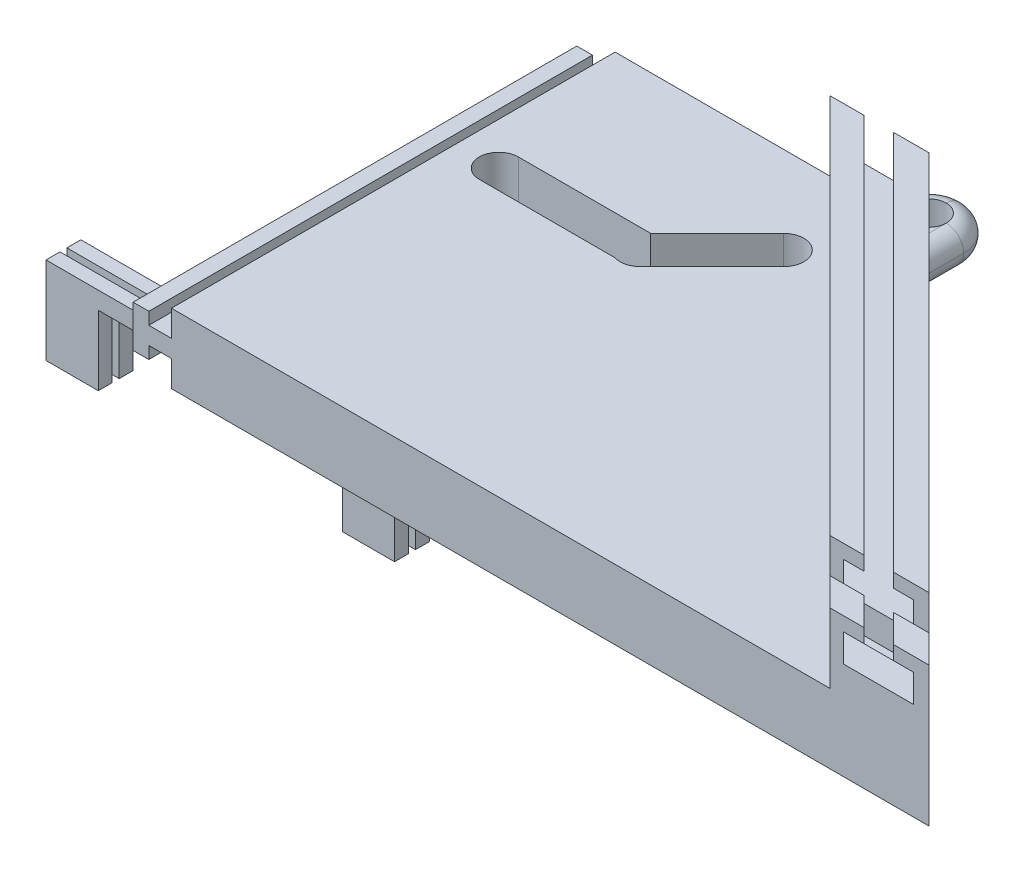
SolidWorks part; units mm, degrees
ref_plane "Front Plane" through (0, 0, 0) normal (0, 0, 1) x (1, 0, 0)
ref_plane "Top Plane" through (0, 0, 0) normal (0, 1, 0) x (1, 0, 0)
ref_plane "Right Plane" through (0, 0, 0) normal (1, 0, 0) x (0, 0, -1)
sketch "Sketch1" plane through (0, 0, 0) normal (0, 1, 0) x (1, 0, 0)
  line L0 (-11.6729, -34.564) -> (96.9667, -34.564)
  line L1 (96.9667, -34.564) -> (33.3271, 29.0756)
  line L2 (33.3271, 29.0756) -> (-11.6729, 29.0756)
  line L3 (-11.6729, 29.0756) -> (-11.6729, -34.564)
  dimension "D1" = 45
  dimension "D2" = 45
  dimension "D3" = 90
extrude "Boss-Extrude1" add sketch "Sketch1" along normal blind 10
sketch "Sketch2" plane through (0, 0, 34.564) normal (0, 0, 1) x (1, 0, 0)
  line L0 (-11.6729, 3.75) -> (-14.9229, 3.75)
  line L1 (-11.6729, 10) -> (-11.6729, 0) construction
  line L2 (-14.9229, 3.75) -> (-14.9229, 2)
  line L3 (-14.9229, 2) -> (-17.1729, 2)
  line L4 (-17.1729, 2) -> (-17.1729, 8)
  line L5 (-17.1729, 8) -> (-14.9229, 8)
  line L6 (-14.9229, 8) -> (-14.9229, 6.25)
  line L7 (-14.9229, 6.25) -> (-11.6729, 6.25)
  line L8 (-11.6729, 6.25) -> (-11.6729, 3.75)
  line L9 (-11.6729, 0) -> (96.9667, 0) construction
  line L10 (-11.6729, 10) -> (96.9667, 10) construction
  dimension "D1" = 3.75
  dimension "D2" = 3.75
  dimension "D3" = 1.75
  dimension "D4" = 1.75
  dimension "D5" = 2.25
  dimension "D6" = 3.25
  dimension "D7" = 3.25
extrude "Boss-Extrude3" add sketch "Sketch2" against normal blind 65
sketch "Sketch3" plane through (0, 8, 0) normal (0, 1, 0) x (1, 0, 0)
  line L0 (33.3271, 29.0756) -> (-11.6729, 29.0756) construction
  line L1 (-17.1729, 30.436) -> (-10.6059, 30.436)
  line L2 (-17.1729, 30.436) -> (-17.1729, 29.0756)
  line L3 (-17.1729, 29.0756) -> (-10.6059, 29.0756)
  line L4 (-10.6059, 30.436) -> (-10.6059, 29.0756)
  dimension "D1" = 0
extrude "Cut-Extrude2" cut sketch "Sketch3" against normal blind 65
sketch "Sketch4" plane through (0, 10, 0) normal (0, 1, 0) x (1, 0, 0)
  line L0 (91.6634, -34.564) -> (28.0238, 29.0756)
  line L1 (-11.6729, -34.564) -> (96.9667, -34.564) construction
  line L2 (33.3271, 29.0756) -> (-11.6729, 29.0756) construction
  line L3 (28.0238, 29.0756) -> (25.5206, 29.0756)
  line L4 (25.5206, 29.0756) -> (89.1602, -34.564)
  line L5 (89.1602, -34.564) -> (91.6634, -34.564)
  line L6 (96.9667, -34.564) -> (33.3271, 29.0756) construction
  dimension "D1" = 3.75
  dimension "D2" = 1.77
extrude "Boss-Extrude4" add sketch "Sketch4" along normal blind 3.25
sketch "Sketch6" plane through (0, 13.25, 0) normal (0, 1, 0) x (1, 0, 0)
  line L0 (90.4118, -34.564) -> (94.1368, -34.564)
  line L1 (89.1602, -34.564) -> (91.6634, -34.564) construction
  line L2 (94.1368, -34.564) -> (30.4972, 29.0756)
  line L3 (30.4972, 29.0756) -> (23.0472, 29.0756)
  line L4 (23.0472, 29.0756) -> (86.6868, -34.564)
  line L5 (86.6868, -34.564) -> (90.4118, -34.564)
  line L6 (28.0238, 29.0756) -> (25.5206, 29.0756) construction
  dimension "D1" = 7.45
  dimension "D2" = 3.725
  dimension "D3" = 3.725
  dimension "D4" = 0
  dimension "D5" = 45
extrude "Boss-Extrude5" add sketch "Sketch6" along normal blind 2.25
sketch "Sketch7" plane through (0, 0, -29.0756) normal (0, 0, -1) x (-1, 0, 0)
  line L0 (-33.3271, 10) -> (-33.3271, 0) construction
  line L1 (-33.3271, 2.5) -> (-23.3271, 2.5)
  line L2 (-33.3271, 2.5) -> (-33.3271, 7.5)
  line L3 (-33.3271, 7.5) -> (-23.3271, 7.5)
  line L4 (-23.3271, 2.5) -> (-23.3271, 7.5)
  line L5 (-33.3271, 0) -> (11.6729, 0) construction
  dimension "D1" = 10
  dimension "D2" = 5
  dimension "D3" = 2.5
extrude "Boss-Extrude6" add sketch "Sketch7" along normal blind 10
sketch "Sketch8" plane through (0, 7.5, 0) normal (0, 1, 0) x (1, 0, 0)
  line L0 (23.3271, 39.0756) -> (33.3271, 39.0756) construction
  line L1 (23.3271, 39.0756) -> (23.3271, 29.0756) construction
  circle A0 centre (28.3271, 34.0756) radius 2.5
  dimension "D1" = 5
  dimension "D2" = 5
  dimension "D3" = 5
extrude "Cut-Extrude3" cut sketch "Sketch8" against normal blind 10
fillet "Fillet1" radius 5 1 edges at (23.3271, 5, -39.0756) type face fillet first side face at (23.3271, 5, -34.0756) second side face at (28.3271, 5, -39.0756)
fillet "Fillet2" radius 5 1 edges at (33.3271, 5, -39.0756) type face fillet first side face at (30.8271, 5, -39.0756) second side face at (33.3271, 5, -34.0756)
fillet "Fillet4" radius 2.5 2 edges at (24.7916, 7.5, -37.6112) (23.3271, 7.5, -31.5756) type face fillet first side face at (25.3093, 5, -37.0934) first side face at (23.3271, 5, -31.5756) second side face at (28.3271, 7.5, -31.5756)
fillet "Fillet5" radius 2.5 2 edges at (24.7916, 2.5, -37.6112) (23.3271, 2.5, -31.5756) type face fillet first side face at (25.3093, 3.75, -37.0934) first side face at (23.3271, 3.75, -31.5756) second side face at (28.3271, 2.5, -31.5756)
sketch "Sketch9" plane through (0, 0, 34.564) normal (0, 0, 1) x (1, 0, 0)
  line L0 (-11.6729, 10) -> (89.1602, 10) construction
  line L1 (94.1368, 15.5) -> (-5.8632, 15.5)
  line L2 (94.1368, 15.5) -> (94.1368, 10)
  line L3 (94.1368, 10) -> (-5.8632, 10)
  line L4 (-5.8632, 15.5) -> (-5.8632, 10)
  dimension "D1" = 100
extrude "Cut-Extrude4" cut sketch "Sketch9" against normal blind 100
sketch "Sketch10" plane through (0, 10, 0) normal (0, 1, 0) x (1, 0, 0)
  line L0 (96.9667, -34.564) -> (89.8956, -41.6351)
  line L1 (89.8956, -41.6351) -> (7.417, 40.8436)
  line L2 (7.417, 40.8436) -> (14.4881, 47.9146)
  line L3 (14.4881, 47.9146) -> (96.9667, -34.564)
  dimension "D1" = 10
extrude "Boss-Extrude7" add sketch "Sketch10" along normal blind 10
sketch "Sketch11" plane through (65.7653, 0, 65.7653) normal (0.7071, 0, 0.7071) x (0.7071, 0, -0.7071)
  line L0 (40.5425, 20) -> (40.5425, 18)
  line L1 (34.1254, 20) -> (44.1254, 20) construction
  line L2 (40.5425, 18) -> (42.5925, 18)
  line L3 (42.5925, 18) -> (42.5925, 14)
  line L4 (42.5925, 14) -> (35.4925, 14)
  line L5 (35.4925, 14) -> (35.4925, 18)
  line L6 (35.4925, 18) -> (37.5425, 18)
  line L7 (37.5425, 18) -> (37.5425, 20)
  line L8 (37.5425, 20) -> (40.5425, 20)
  dimension "D1" = 2
  dimension "D2" = 7.1
  dimension "D3" = 3
  dimension "D4" = 2.05
  dimension "D5" = 4
extrude "Cut-Extrude5" cut sketch "Sketch11" against normal blind 150
sketch "Sketch12" plane through (0, 10, 0) normal (0, -1, 0) x (-1, 0, 0)
  line L0 (-33.3271, 29.0756) -> (-19.185, 29.0756) construction
  line L1 (-19.185, 29.0756) -> (-49.1058, 29.0756)
  line L2 (-19.185, 29.0756) -> (-19.185, 62.2793)
  line L3 (-19.185, 62.2793) -> (-49.1058, 62.2793)
  line L4 (-49.1058, 29.0756) -> (-49.1058, 62.2793)
extrude "Cut-Extrude6" cut sketch "Sketch12" against normal blind 150
sketch "Sketch14" plane through (0, 10, 0) normal (0, -1, 0) x (-1, 0, 0)
  line L0 (-19.185, 29.0756) -> (-19.185, 43.2178) construction
  line L1 (-19.185, 29.0756) -> (0, 29.0756)
  line L2 (-19.185, 29.0756) -> (-19.185, 57.2083)
  line L3 (-19.185, 57.2083) -> (0, 57.2083)
  line L4 (0, 29.0756) -> (0, 57.2083)
extrude "Cut-Extrude7" cut sketch "Sketch14" against normal blind 150
sketch "Sketch16" plane through (0, 10, 0) normal (0, -1, 0) x (-1, 0, 0)
  line L1 (-82.8246, -34.564) -> (-98.445, -34.564)
  line L2 (-82.8246, -34.564) -> (-82.8246, -45.3868)
  line L3 (-82.8246, -45.3868) -> (-98.445, -45.3868)
  line L4 (-98.445, -34.564) -> (-98.445, -45.3868)
extrude "Cut-Extrude8" cut sketch "Sketch16" against normal blind 150
sketch "Sketch17" plane through (0, 20, 0) normal (0, 1, 0) x (1, 0, 0)
  line L0 (92.9667, -30.564) -> (78.8246, -30.564)
  line L1 (96.9667, -34.564) -> (33.3271, 29.0756) construction
  line L2 (19.185, 29.0756) -> (82.8246, -34.564) construction
  line L3 (78.8246, -30.564) -> (73.8246, -25.564)
  line L4 (73.8246, -25.564) -> (87.9667, -25.564)
  line L5 (87.9667, -25.564) -> (92.9667, -30.564)
  line L6 (82.8246, -34.564) -> (87.6572, -34.564) construction
  dimension "D1" = 4
  dimension "D2" = 5
extrude "Cut-Extrude9" cut sketch "Sketch17" against normal blind 10
sketch "Sketch18" plane through (0, 10, 0) normal (0, 1, 0) x (1, 0, 0)
  line L0 (24.9905, 16.5621) -> (14.7427, 6.3142) construction
  line L1 (27.059, 14.4936) -> (16.8112, 4.2458)
  line L2 (22.9221, 18.6306) -> (12.6742, 8.3827)
  line L3 (14.7427, 6.3142) -> (-5.5955, 6.3142) construction
  line L4 (14.7427, 3.5173) -> (-5.5955, 3.5173)
  line L5 (14.7427, 9.1112) -> (-5.5955, 9.1112)
  arc A0 (27.059, 14.4936) -> (22.9221, 18.6306) centre (24.9905, 16.5621) ccw
  arc A1 (12.6742, 8.3827) -> (16.8112, 4.2458) centre (14.7427, 6.3142) ccw
  arc A2 (14.7427, 3.5173) -> (14.7427, 9.1112) centre (14.7427, 6.3142) ccw
  arc A3 (-5.5955, 9.1112) -> (-5.5955, 3.5173) centre (-5.5955, 6.3142) ccw
  point P2 (19.8666, 11.4382)
  point P7 (4.5736, 6.3142)
extrude "Cut-Extrude10" cut sketch "Sketch18" against normal blind 10 contours A2 L4 A1 L1 A0 L2 L5 | L4 A2 L5 L2 A1 | L4 A3 L5 A2 region at (21.4219, 10, -12.9652) region at (14.6577, 10, -6.3239)
sketch "Sketch19" plane through (0, 0, 0) normal (0, -1, 0) x (-1, 0, 0)
  line L0 (11.6729, -34.564) -> (-96.9667, -34.564) construction
  line L1 (-13.3271, -22.564) -> (36.6729, -22.564)
  line L2 (-13.3271, -22.564) -> (-13.3271, -24.564)
  line L3 (-13.3271, -24.564) -> (36.6729, -24.564)
  line L4 (36.6729, -22.564) -> (36.6729, -24.564)
  line L5 (11.6729, 29.0756) -> (11.6729, -34.564) construction
  line L7 (-13.3271, -25.564) -> (36.6729, -25.564)
  line L8 (-13.3271, -25.564) -> (-13.3271, -27.564)
  line L9 (-13.3271, -27.564) -> (36.6729, -27.564)
  line L10 (36.6729, -25.564) -> (36.6729, -27.564)
  line L11 (-13.3271, -22.564) -> (-3.3271, -22.564)
  line L12 (-13.3271, -22.564) -> (-13.3271, -24.564)
  line L13 (-13.3271, -24.564) -> (-3.3271, -24.564)
  line L14 (-3.3271, -22.564) -> (-3.3271, -24.564)
  line L15 (-13.3271, -25.564) -> (-3.3271, -25.564)
  line L16 (-13.3271, -25.564) -> (-13.3271, -27.564)
  line L17 (-13.3271, -27.564) -> (-3.3271, -27.564)
  line L18 (-3.3271, -25.564) -> (-3.3271, -27.564)
  line L19 (36.6729, -22.564) -> (26.6729, -22.564)
  line L20 (36.6729, -22.564) -> (36.6729, -24.564)
  line L21 (36.6729, -24.564) -> (26.6729, -24.564)
  line L22 (26.6729, -22.564) -> (26.6729, -24.564)
  line L23 (36.6729, -25.564) -> (26.6729, -25.564)
  line L24 (36.6729, -25.564) -> (36.6729, -27.564)
  line L25 (36.6729, -27.564) -> (26.6729, -27.564)
  line L26 (26.6729, -25.564) -> (26.6729, -27.564)
  line M20 (11.6729, -34.564) -> (11.6729, 29.0756)
  dimension "D1" = 50
  dimension "D2" = 2
  dimension "D3" = 10
  dimension "D4" = 25
  dimension "D5" = 50
  dimension "D6" = 2
  dimension "D7" = 1
  dimension "D8" = 10
  dimension "D9" = 10
  dimension "D10" = 10
  dimension "D11" = 10
extrude "Boss-Extrude9" add sketch "Sketch19" along normal blind 2.5 contours L18 L7 L8 L9 | L14 L1 L2 L3 | L7 L26 L9 L10 | L1 L22 L3 L4 | L7 L18 L9 M20 | L1 L14 L3 M20 | L26 L7 L9 M20 | L22 L1 L3 M20 region at (-19.1729, 0, 26.564) region at (-4.1729, 0, 26.564) region at (8.3271, 0, 23.564) region at (-4.1729, 0, 23.564) region at (-19.1729, 0, 23.564) region at (-31.6729, 0, 23.564) region at (8.3271, 0, 26.564) region at (-31.6729, 0, 26.564)
sketch "Sketch21" plane through (0, -2.5, 0) normal (0, -1, 0) x (-1, 0, 0)
  line L0 (-13.3271, -24.564) -> (36.6729, -24.564) construction
  line L1 (-13.3271, -22.564) -> (-5.8271, -22.564)
  line L2 (-13.3271, -22.564) -> (-13.3271, -24.564)
  line L3 (-13.3271, -24.564) -> (-5.8271, -24.564)
  line L4 (-5.8271, -22.564) -> (-5.8271, -24.564)
  line L5 (-13.3271, -25.564) -> (-13.3271, -27.564) construction
  line L6 (-13.3271, -25.564) -> (-5.8271, -25.564)
  line L7 (-13.3271, -25.564) -> (-13.3271, -27.564)
  line L8 (-13.3271, -27.564) -> (-5.8271, -27.564)
  line L9 (-5.8271, -25.564) -> (-5.8271, -27.564)
  line L10 (-13.3271, -25.564) -> (36.6729, -25.564) construction
  line L11 (-13.3271, -27.564) -> (36.6729, -27.564) construction
  line L13 (36.6729, -25.564) -> (29.1729, -25.564)
  line L14 (36.6729, -25.564) -> (36.6729, -27.564)
  line L15 (36.6729, -27.564) -> (29.1729, -27.564)
  line L16 (29.1729, -25.564) -> (29.1729, -27.564)
  line L17 (36.6729, -22.564) -> (29.1729, -22.564)
  line L18 (36.6729, -22.564) -> (36.6729, -24.564)
  line L19 (36.6729, -24.564) -> (29.1729, -24.564)
  line L20 (29.1729, -22.564) -> (29.1729, -24.564)
  dimension "D1" = 7.5
  dimension "D2" = 7.5
  dimension "D3" = 7.5
  dimension "D4" = 7.5
extrude "Boss-Extrude10" add sketch "Sketch21" along normal blind 10
